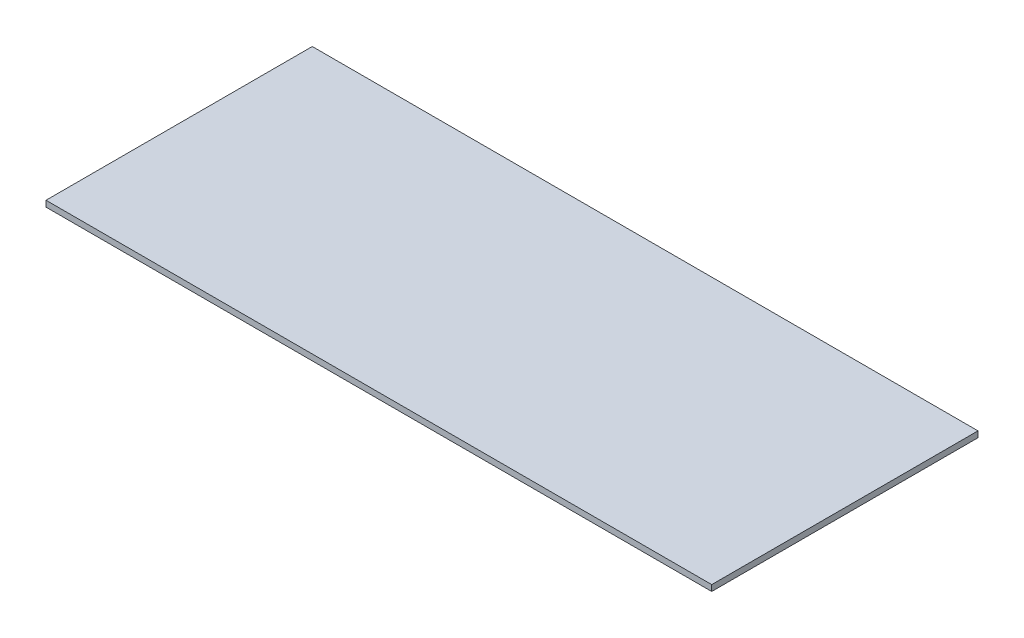
SolidWorks part; units mm, degrees
material "ABS"
ref_plane "Front Plane" through (0, 0, 0) normal (0, 0, 1) x (1, 0, 0)
ref_plane "Top Plane" through (0, 0, 0) normal (0, 1, 0) x (1, 0, 0)
ref_plane "Right Plane" through (0, 0, 0) normal (1, 0, 0) x (0, 0, -1)
sketch "Sketch1" plane through (0, 0, 0) normal (0, 1, 0) x (1, 0, 0)
  line L1 (0, 0) -> (2000, 0)
  line L2 (0, 0) -> (0, 800)
  line L3 (0, 800) -> (2000, 800)
  line L4 (2000, 0) -> (2000, 800)
  dimension "D1" = 800
  dimension "D2" = 2000
extrude "Boss-Extrude1" add sketch "Sketch1" along normal blind 18
